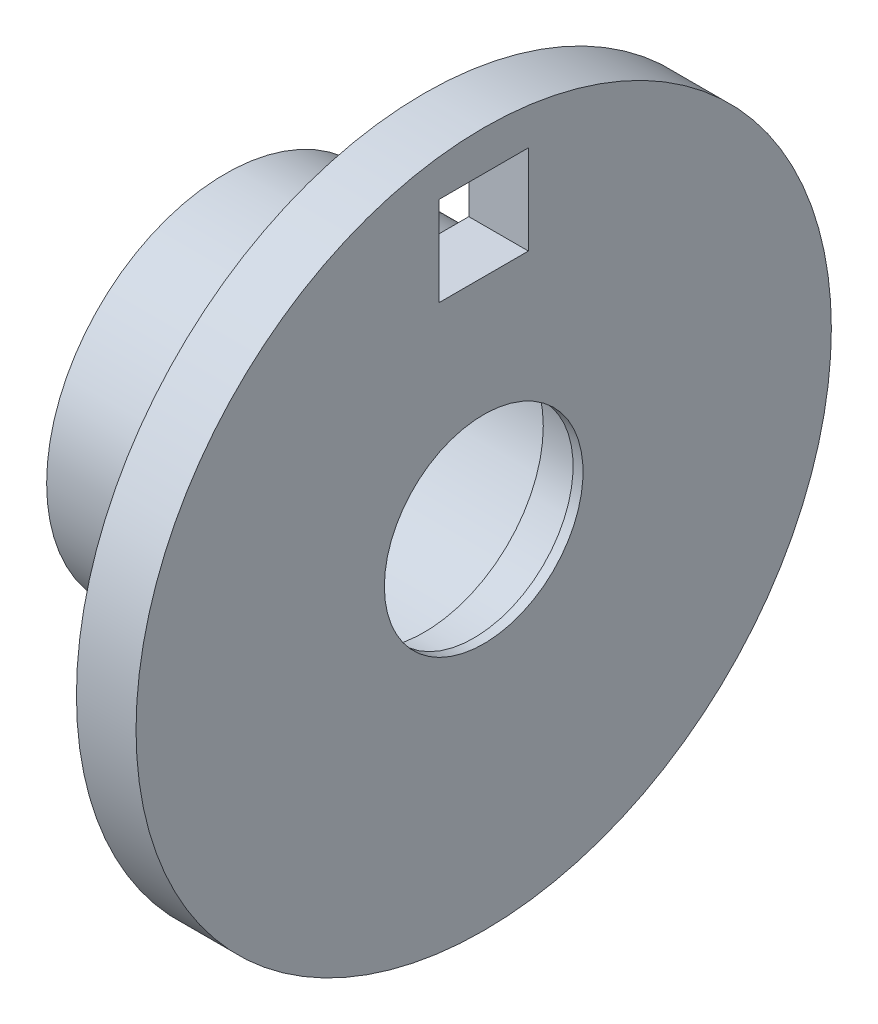
SolidWorks part; units mm, degrees
ref_plane "Front Plane" through (0, 0, 0) normal (0, 0, 1) x (1, 0, 0)
ref_plane "Top Plane" through (0, 0, 0) normal (0, 1, 0) x (1, 0, 0)
ref_plane "Right Plane" through (0, 0, 0) normal (1, 0, 0) x (0, 0, -1)
sketch "Sketch1" plane through (0, 0, 0) normal (0, 0, 1) x (1, 0, 0)
  line L0 (-42.8096, 0) -> (42.8096, 0) construction
  line L1 (-1, 12) -> (-6, 12)
  line L2 (-6, 12) -> (-6, 16)
  line L3 (-6, 16) -> (-26, 16)
  line L4 (-26, 16) -> (-26, 18)
  line L6 (0, 35) -> (0, 10)
  line L9 (0, 10) -> (-1, 10)
  line L10 (-1, 10) -> (-1, 12)
  line L11 (-26, 18) -> (-6, 18)
  line L12 (-6, 18) -> (-6, 35)
  line L13 (-6, 35) -> (0, 35)
  point P3 (0, 0)
  point P4 (0, 0)
  dimension "D1" = 2
  dimension "D2" = 6
  dimension "D3" = 5
  dimension "D4" = 24
  dimension "D5" = 32
  dimension "D6" = 2
  dimension "D7" = 70
  dimension "D8" = 6
  dimension "D9" = 20
revolve "Revolve1" add sketch "Sketch1" angle 360 about L0
sketch "Sketch2" plane through (0, 0, 0) normal (1, 0, 0) x (0, 0, -1)
  line L0 (0, 35) -> (0, 18) construction
  line L3 (0, 35) -> (0, 10) construction
  line L5 (-4.5, 22) -> (4.5, 22)
  line L6 (-4.5, 22) -> (-4.5, 31)
  line L7 (-4.5, 31) -> (4.5, 31)
  line L8 (4.5, 22) -> (4.5, 31)
  line L9 (-4.5, 22) -> (4.5, 31) construction
  line L10 (-4.5, 31) -> (4.5, 22) construction
  point P3 (0, 26.5)
  point P5 (0, 26.5)
  dimension "D1" = 9
extrude "Cut-Extrude1" cut sketch "Sketch2" against normal up to surface (6 mm away) up to face at (-6, 0, 18)
